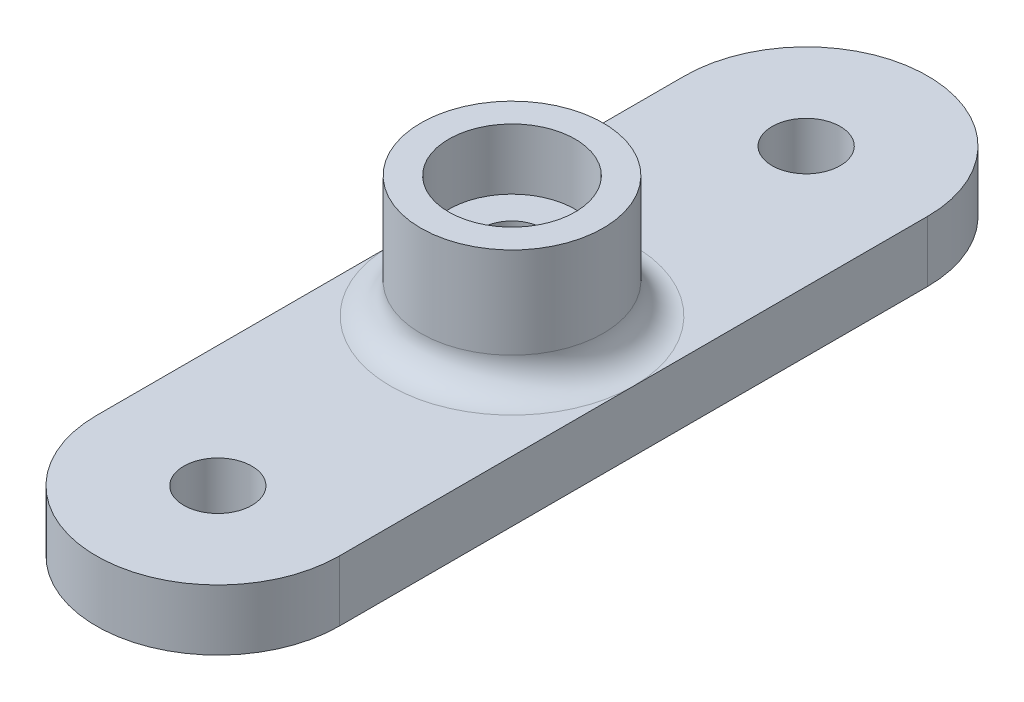
SolidWorks part; units mm, degrees
ref_plane "Front Plane" through (0, 0, 0) normal (0, 0, 1) x (1, 0, 0)
ref_plane "Top Plane" through (0, 0, 0) normal (0, 1, 0) x (1, 0, 0)
ref_plane "Right Plane" through (0, 0, 0) normal (1, 0, 0) x (0, 0, -1)
sketch "Sketch1" plane through (0, 0, 0) normal (0, 1, 0) x (1, 0, 0)
  line L0 (0, 15.367) -> (0, -15.367) construction
  line L1 (0, 15.367) -> (0, -15.367) construction
  line L2 (6.35, 15.367) -> (6.35, -15.367)
  line L3 (-6.35, 15.367) -> (-6.35, -15.367)
  circle A0 centre (0, 15.367) radius 1.778
  circle A1 centre (0, -15.367) radius 1.778
  arc A2 (6.35, 15.367) -> (-6.35, 15.367) centre (0, 15.367) ccw
  arc A3 (-6.35, -15.367) -> (6.35, -15.367) centre (0, -15.367) ccw
  circle A4 centre (0, 0) radius 1.5875
  point P2 (0, 0)
  point P6 (0, 0)
  dimension "D2" = 3.556
  dimension "D4" = 3.175
  dimension "D1" = 30.734
  dimension "D3" = 12.7
extrude "Boss-Extrude1" add sketch "Sketch1" along normal blind 3.175
sketch "Sketch2" plane through (0, 3.175, 0) normal (0, 1, 0) x (1, 0, 0)
  circle A0 centre (0, 0) radius 4.7625
  circle A3 centre (0, 0) radius 1.5875
  circle A4 centre (0, 0) radius 1.5875 construction
  dimension "D1" = 9.525
extrude "Boss-Extrude2" add sketch "Sketch2" along normal offset from surface (6.35 mm away) 9.525 up to face at (0, 0, 0)
sketch "Sketch3" plane through (0, 9.525, 0) normal (0, 1, 0) x (1, 0, 0)
  circle A0 centre (0, 0) radius 3.302
  dimension "D1" = 6.604
extrude "Cut-Extrude1" cut sketch "Sketch3" against normal blind 3.175
fillet "Fillet1" radius 1.5875 1 edges at (0, 3.175, 4.7625)
